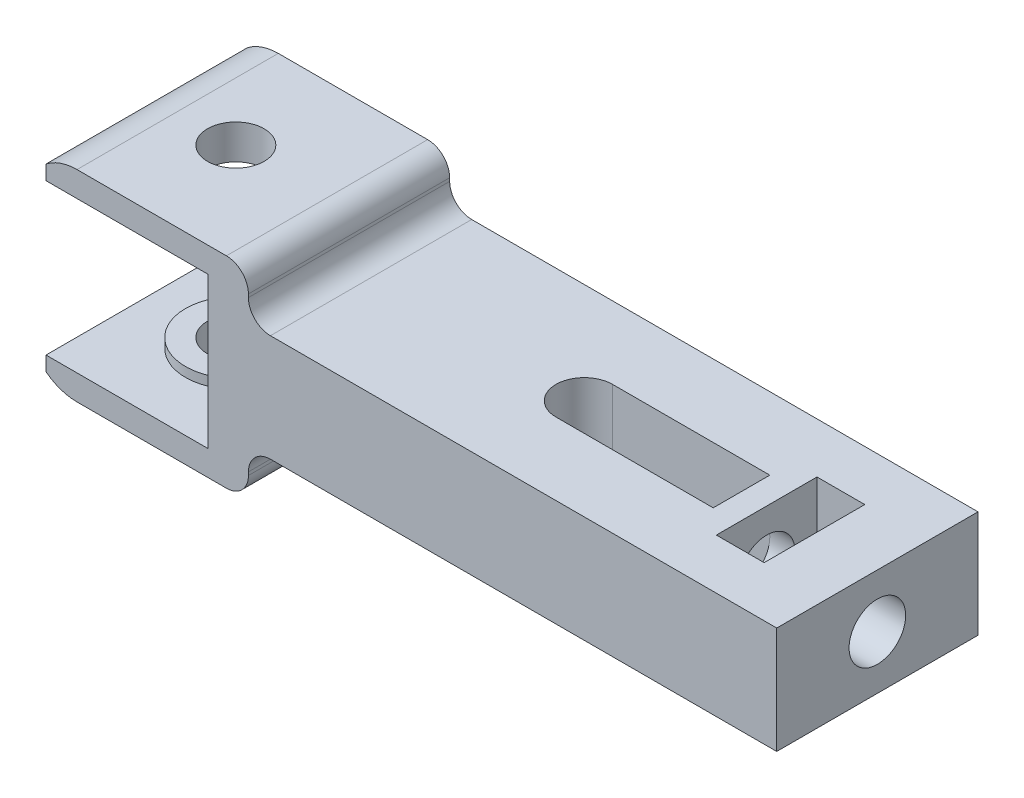
SolidWorks part; units mm, degrees
ref_plane "Front Plane" through (0, 0, 0) normal (0, 0, 1) x (1, 0, 0)
ref_plane "Top Plane" through (0, 0, 0) normal (0, 1, 0) x (1, 0, 0)
ref_plane "Right Plane" through (0, 0, 0) normal (1, 0, 0) x (0, 0, -1)
sketch "Sketch1" plane through (0, 0, 0) normal (0, 0, 1) x (1, 0, 0)
  line L0 (0, 0) -> (-42, 0)
  line L1 (-42, 0) -> (-42, 3.75)
  line L2 (-42, 3.75) -> (-59.5, 3.75)
  line L3 (-59.5, 3.75) -> (-59.5, 0.75)
  line L4 (-59.5, 0.75) -> (-45.5, 0.75)
  line L5 (-45.5, 0.75) -> (-45.5, -9.25)
  line L6 (0, 0) -> (0, -8.5)
  line L7 (0, -4.25) -> (-45.5, -4.25) construction
  line L8 (-59.5, -9.25) -> (-45.5, -9.25)
  line L9 (-59.5, -12.25) -> (-59.5, -9.25)
  line L10 (-42, -12.25) -> (-59.5, -12.25)
  line L11 (-42, -8.5) -> (-42, -12.25)
  line L12 (0, -8.5) -> (-42, -8.5)
  dimension "D1" = 59.5
  dimension "D2" = 14
  dimension "D3" = 4.25
  dimension "D4" = 5
  dimension "D5" = 3
  dimension "D6" = 17.5
extrude "Boss-Extrude1" add sketch "Sketch1" along normal blind 16
sketch "Sketch2" plane through (0, 0, 0) normal (0, 1, 0) x (1, 0, 0)
  line L0 (0, -8) -> (-42, -8) construction
  line L1 (0, -16) -> (0, 0) construction
  line L2 (-42, -16) -> (-42, 0) construction
  line L4 (-8.8, -4) -> (-5, -4)
  line L5 (-8.8, -4) -> (-8.8, -12)
  line L6 (-8.8, -12) -> (-5, -12)
  line L7 (-5, -4) -> (-5, -12)
  line L8 (-8.8, -4) -> (-5, -12) construction
  line L9 (-8.8, -12) -> (-5, -4) construction
  line L10 (-23.3, -10.25) -> (-10.8, -10.25)
  line L12 (-23.3, -5.75) -> (-10.8, -5.75)
  line L13 (-10.8, -10.25) -> (-10.8, -5.75)
  line L14 (-23.3, -10.25) -> (-10.8, -5.75) construction
  line L15 (-23.3, -5.75) -> (-10.8, -10.25) construction
  arc A0 (-23.3, -5.75) -> (-23.3, -10.25) centre (-23.3, -8) ccw
  point P6 (-6.9, -8)
  point P11 (-17.05, -8)
  dimension "D7" = 2.25
  dimension "D1" = 8
  dimension "D2" = 3.8
  dimension "D3" = 5
  dimension "D4" = 2
  dimension "D5" = 4.5
  dimension "D6" = 12.5
extrude "Cut-Extrude1" cut sketch "Sketch2" against normal through all
sketch "Sketch3" plane through (0, 0, 0) normal (1, 0, 0) x (0, 0, -1)
  line L0 (-8, 0) -> (-8, -8.5) construction
  line L1 (-16, 0) -> (0, 0) construction
  line L2 (-16, -8.5) -> (0, -8.5) construction
  circle A0 centre (-8, -4.25) radius 2.25
  dimension "D1" = 4.5
extrude "Cut-Extrude2" cut sketch "Sketch3" against normal up to surface (10.8 mm away) up to face at (-10.8, -4.25, 8)
fillet "Fillet1" radius 1.75 4 edges at (-42, -8.5, 8) (-42, 3.75, 8) (-42, 0, 8) (-42, -12.25, 8)
sketch "Sketch4" plane through (0, -9.25, 0) normal (0, 1, 0) x (1, 0, 0)
  line L0 (-59.5, -8) -> (-43.75, -8) construction
  line L1 (-59.5, -16) -> (-59.5, 0) construction
  line L2 (-43.75, 0) -> (-43.75, -16) construction
  circle A0 centre (-51.625, -8) radius 9.25
  dimension "D1" = 18.5
extrude "Cut-Extrude3" cut sketch "Sketch4" along normal up to surface (10 mm away) up to face at (-52.5, 0.75, 8)
sketch "Sketch5" plane through (0, 3.75, 0) normal (0, 1, 0) x (1, 0, 0)
  line L0 (-59.5, -8) -> (-43.75, -8) construction
  line L1 (-59.5, -16) -> (-59.5, 0) construction
  line L2 (-43.75, -16) -> (-43.75, 0) construction
  circle A0 centre (-51, -8) radius 2.25
  dimension "D1" = 4.5
  dimension "D2" = 8.5
extrude "Cut-Extrude4" cut sketch "Sketch5" against normal through all
fillet "Fillet2" radius 4 2 edges at (-59.5, -12.25, 8) (-59.5, 3.75, 8)
sketch "Sketch6" plane through (0, -9.25, 0) normal (0, 1, 0) x (1, 0, 0)
  line L0 (-51.625, 1.25) -> (-59.5, 1.25)
  line L1 (-59.5, -16) -> (-59.5, 0) construction
  line L2 (-51.625, -17.25) -> (-59.5, -17.25)
  line L3 (-59.5, -17.25) -> (-59.5, 1.25)
  arc A0 (-51.625, -17.25) -> (-51.625, 1.25) centre (-51.625, -8) ccw
  arc A1 (-45.5, -14.9316) -> (-45.5, -1.0684) centre (-51.625, -8) ccw construction
extrude "Cut-Extrude5" cut sketch "Sketch6" against normal blind 1
sketch "Sketch7" plane through (0, -10.25, 0) normal (0, 1, 0) x (1, 0, 0)
  circle A0 centre (-51, -8) radius 4
  circle A1 centre (-51, -8) radius 2.25
  circle A2 centre (-51, -8) radius 2.25 construction
  dimension "D1" = 8
extrude "Boss-Extrude2" add sketch "Sketch7" along normal blind 0.75
ref_plane "Plane1" through (0, -4.25, 0) normal (0, 1, 0) x (1, 0, 0)
mirror "Mirror1" about plane through (0, -4.25, 0) normal (0, 1, 0) of "Boss-Extrude2", "Cut-Extrude5"
sketch "Sketch8" plane through (0, 0, 16) normal (0, 0, 1) x (1, 0, 0)
  line L0 (0, -4.25) -> (-60.0911, -4.25) construction
  line L1 (0, -8.5) -> (0, 0) construction
  line L2 (8.8, -4.25) -> (-8.8, -4.25) construction
  line L3 (-43.75, 3.75) -> (-55.627, 3.75) construction
  line L4 (-62.0911, -12.25) -> (-58.0911, -12.25)
  line L5 (-62.0911, -12.25) -> (-62.0911, 3.75)
  line L6 (-62.0911, 3.75) -> (-58.0911, 3.75)
  line L7 (-58.0911, -12.25) -> (-58.0911, 3.75)
  line L8 (-62.0911, -12.25) -> (-58.0911, 3.75) construction
  line L9 (-62.0911, 3.75) -> (-58.0911, -12.25) construction
  dimension "D1" = 1
  dimension "D2" = 2
extrude "Cut-Extrude6" cut sketch "Sketch8" against normal through all
sketch "Sketch9" plane through (0, 0, 16) normal (0, 0, 1) x (1, 0, 0)
  line L0 (-58.0911, -10.25) -> (-46.9815, -10.25) construction
  line L1 (-46.9815, 1.75) -> (-45.2315, 1.75)
  line L2 (-46.9815, 1.75) -> (-46.9815, -10.25)
  line L3 (-46.9815, -10.25) -> (-45.2315, -10.25)
  line L4 (-45.2315, 1.75) -> (-45.2315, -10.25)
  dimension "D1" = 1.75
extrude "Cut-Extrude7" cut sketch "Sketch9" against normal through all
equation "\"X-ROD-SPACING\"=45"
equation "\"Y-ROD-SPACING\"=75"
equation "\"Z-ROD-SPACING\"=17.5"
equation "\"Y-BED-OFFSET\"=2"
equation "\"Y-BED-ROD-INSET\"=3.5"
equation "\"T-SLOT-NUT-FILLET-RADIUS\"=0.5"
equation "\"T-SLOT-SCREW-SHAFT-RADIUS\"=1.55"
equation "\"T-SLOT-SCREW-SHAFT-CUTOUT-LENGTH\"=11"
equation "\"T-SLOT-NUT-DEPTH\"=3.5"
equation "\"T-SLOT-NUT-WIDTH\"=2.85"
equation "\"T-SLOT-NUT-END-DISTANCE\"=8"
equation "\"ACRYLIC-THICKNESS\"=10"
equation "\"ACRYLIC-TAB-CUTOUT-SIZE\"=\"ACRYLIC-THICKNESS\"+\"ACRYLIC-TAB-TOLERANCE\"*2"
equation "\"ACRYLIC-TAB-WIDTH\"=\"ACRYLIC-THICKNESS\""
equation "\"ACRYLIC-M3-HOLE\"=2.9"
equation "\"SMOOTHROD-CAP-SCREW-DISTANCE\"=20"
equation "\"FRAME-WIDTH-INNER\"=370"
equation "\"NEMA17-HOLE-SPACING\"=31"
equation "\"NEMA17-CENTRAL-CUTOUT\"=22.5"
equation "\"Z-BRACKET-REACH\"=57"
equation "\"TOP-BRACKET-SPACING\"=40"
equation "\"SMOOTHROD-X-LENGTH\"=350"
equation "\"SMOOTHROD-Y-LENGTH\"=350"
equation "\"SMOOTHROD-Z-LENGTH\"=350"
equation "\"SMOOTHROD-TIGHTENING-HEADROOM\"=.25"
equation "\"LEADSCREW-Z-LENGTH\"=300"
equation "\"SCREW-HEAD-RADIUS\"=6"
equation "\"PRINTED-X-SMOOTHROD-DIAMETER\"=8.8"
equation "\"PRINTED-X-SMOOTHROD-CUTOUT\"=10"
equation "\"PRINTED-X-BASE-HEIGHT\"=10"
equation "\"PRINTED-LM8UU-CUTOUT-SIZE\"=15.5"
equation "\"PRINTED-LM8UU-CUTOUT-LENGTH\"=24.5"
equation "\"PRINTED-X-IDLER-HEIGHT\"=16"
equation "\"D1@Boss-Extrude1\"=\"PRINTED-X-IDLER-HEIGHT\""
